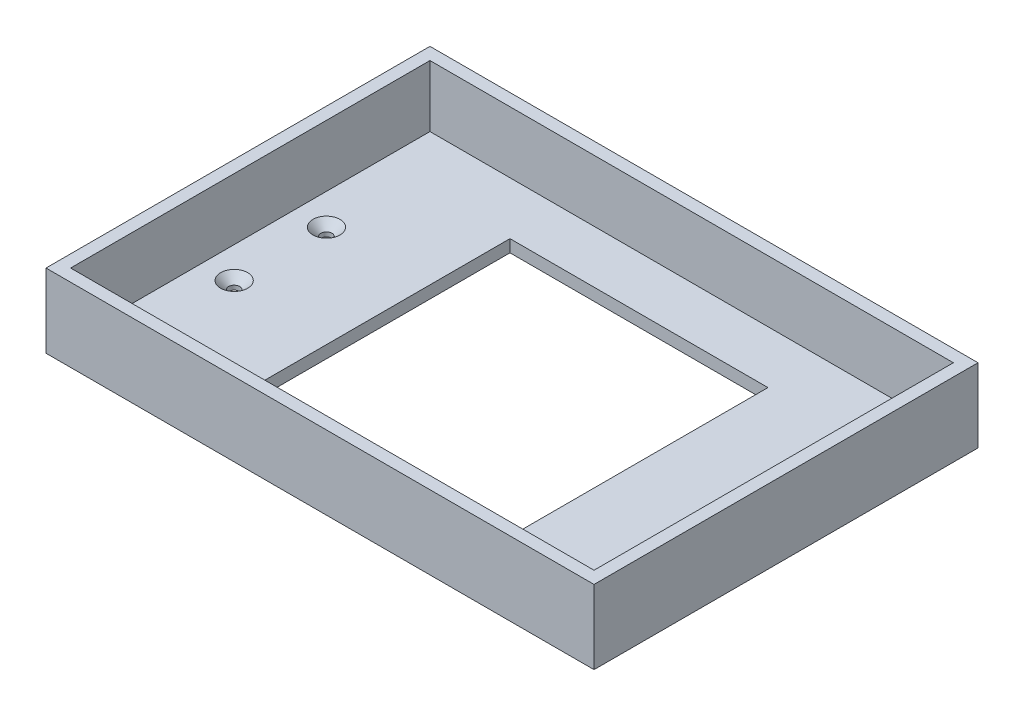
SolidWorks part; units mm, degrees
ref_plane "Front Plane" through (0, 0, 0) normal (0, 0, 1) x (1, 0, 0)
ref_plane "Top Plane" through (0, 0, 0) normal (0, 1, 0) x (1, 0, 0)
ref_plane "Right Plane" through (0, 0, 0) normal (1, 0, 0) x (0, 0, -1)
sketch "Sketch1" plane through (0, 0, 0) normal (0, 1, 0) x (1, 0, 0)
  line L0 (-44.545, -31.21) -> (-44.545, 31.21)
  line L1 (-42.545, -29.21) -> (42.545, -29.21)
  line L2 (-42.545, -29.21) -> (-42.545, 29.21)
  line L3 (-42.545, 29.21) -> (42.545, 29.21)
  line L4 (42.545, -29.21) -> (42.545, 29.21)
  line L5 (-42.545, -29.21) -> (42.545, 29.21) construction
  line L6 (-42.545, 29.21) -> (42.545, -29.21) construction
  line L7 (-44.545, 31.21) -> (44.545, 31.21)
  line L8 (44.545, -31.21) -> (44.545, 31.21)
  line L9 (-44.545, -31.21) -> (44.545, -31.21)
  point P0 (0, 0)
  dimension "D1" = 58.42
  dimension "D2" = 85.09
  dimension "D3" = 2
extrude "Boss-Extrude1" add sketch "Sketch1" against normal blind 2 contours L1 L4 L3 L2 | L0 L9 L8 L7 L4 L1 L2 L3 region at (-43.4572, 0, 0) region at (0, 0, 0)
extrude "Boss-Extrude2" add sketch "Sketch1<3>" along normal blind 10
sketch "Sketch1<3>" plane through (0, 0, 0) normal (0, 1, 0) x (1, 0, 0) same geometry as "Sketch1"
hole_wizard "CSK for M2 Flat Head Machine Screw1" positions "Sketch4" profile "Sketch6" countersink size "M2" standard "ANSI Metric"
sketch "Sketch4" plane through (0, 0, 0) normal (0, 1, 0) x (1, 0, 0)
  line L3 (-37.5, -7.6645) -> (37.5, -7.6645) construction
  line L4 (-37.5, -7.6645) -> (-37.5, 7.3355) construction
  line L5 (-37.5, 7.3355) -> (37.5, 7.3355) construction
  line L6 (37.5, -7.6645) -> (37.5, 7.3355) construction
  point P146 (-37.5, 7.3355)
  point P149 (-37.5, -7.6645)
  point P152 (37.5, -7.6645)
  point P155 (37.5, 7.3355)
sketch "Sketch6" plane through (37.5, 0, -7.3355) normal (1, 0, 0) x (0, 0, 1)
  line L0 (0, 0) -> (0, 10.4468)
  line L1 (0, 10.4468) -> (0.9, 9.906)
  line L2 (0.9, 9.906) -> (0.9, 1.3)
  line L3 (0.9, 1.3) -> (2.2, 0)
  line L5 (2.2, 0) -> (0, 0)
  line L6 (-0.9, 1.3) -> (-2.2, 0) construction
  line L10 (0, 10.4468) -> (-0.9, 9.906) construction
  line L11 (0, -6.35) -> (0, 107.95) construction
  dimension "Hole Dia." = 1.8
  dimension "Hole Depth" = 9.906
  dimension "Near C'Sink Dia." = 4.4
  dimension "Near C'Sink Angle" = 90
  dimension "Drill Angle" = 118
sketch "Sketch7" plane through (0, 0, 0) normal (0, 1, 0) x (1, 0, 0)
  line L1 (-20.9676, -20.6397) -> (20.9676, -20.6397)
  line L2 (-20.9676, -20.6397) -> (-20.9676, 20.6397)
  line L3 (-20.9676, 20.6397) -> (20.9676, 20.6397)
  line L4 (20.9676, -20.6397) -> (20.9676, 20.6397)
  line L5 (-20.9676, -20.6397) -> (20.9676, 20.6397) construction
  line L6 (-20.9676, 20.6397) -> (20.9676, -20.6397) construction
  point P0 (0, 0)
extrude "Cut-Extrude1" cut sketch "Sketch7" against normal blind 2.54
